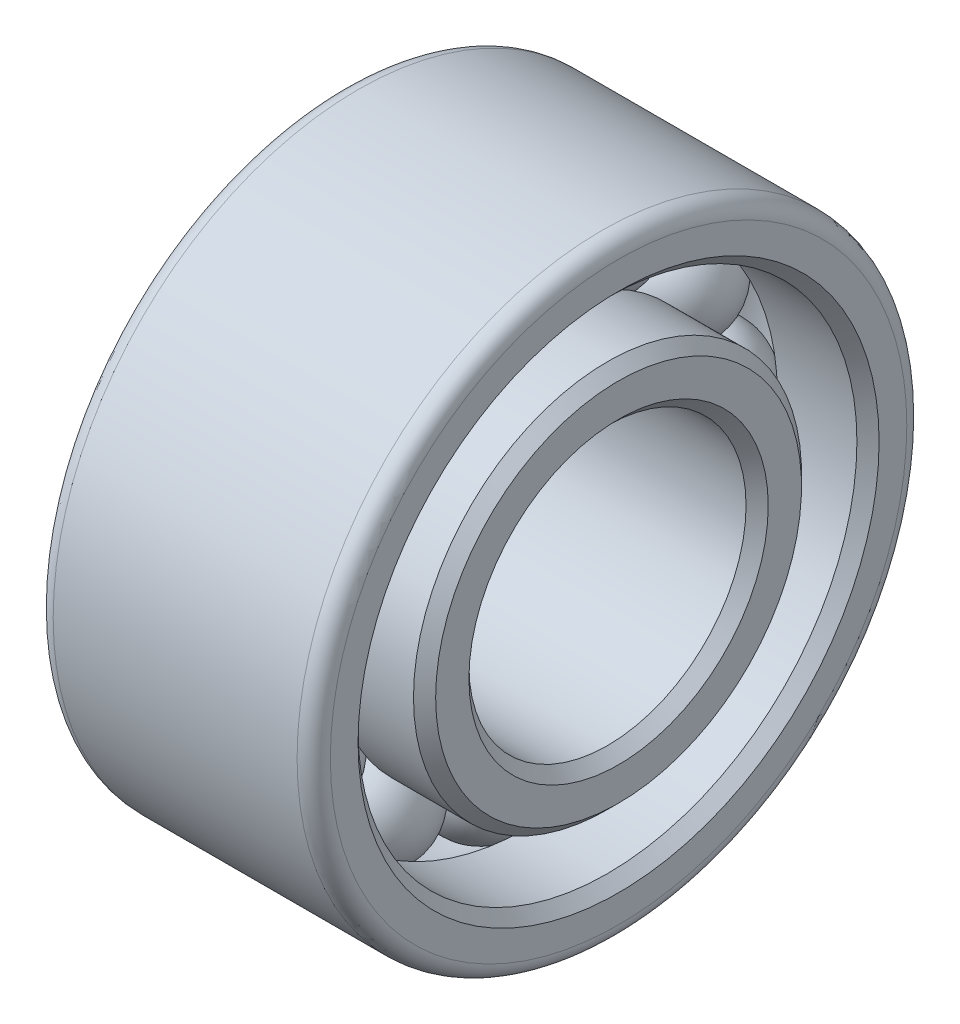
SolidWorks part; units mm, degrees
material "1023 Листовая углеродистая сталь (SS)"
ref_plane "Спереди" through (0, 0, 0) normal (0, 0, 1) x (1, 0, 0)
ref_plane "Сверху" through (0, 0, 0) normal (0, 1, 0) x (1, 0, 0)
ref_plane "Справа" through (0, 0, 0) normal (1, 0, 0) x (0, 0, -1)
sketch "Эскиз1" plane through (0, 0, 0) normal (0, 0, 1) x (1, 0, 0)
  line L0 (-1.0669, -2.5) -> (5.2077, -2.5) construction
  line L1 (0, 0) -> (5, 0)
  line L2 (0, 0) -> (0, 1)
  line L3 (0, 2) -> (1.634, 2)
  line L4 (5, 0) -> (5, 1)
  line L5 (5, 1) -> (3.366, 1)
  line L6 (0, 2) -> (0, 3)
  line L7 (0, 3) -> (5, 3)
  line L8 (5, 2) -> (5, 3)
  line L9 (3.366, 2) -> (5, 2)
  line L10 (1.634, 1) -> (0, 1)
  arc A0 (1.634, 1) -> (3.366, 1) centre (2.5, 1.5) ccw
  arc A1 (3.366, 2) -> (1.634, 2) centre (2.5, 1.5) ccw
  dimension "D7" = 5
  dimension "D2" = 2
  dimension "D8" = 0.5
  dimension "D1" = 2.5
  dimension "D3" = 1
  dimension "D4" = 5
  dimension "D5" = 1
  dimension "D6" = 5.5
revolve "Повернуть1" add sketch "Эскиз1" angle 360 about L0
sketch "Эскиз2" plane through (0, 0, 0) normal (0, 0, 1) x (1, 0, 0)
  line L0 (2.5, 2.5) -> (2.5, 0.5) construction
  line L1 (2.5, 2.5) -> (2.5, 0.5)
  line L2 (5, 3) -> (0, 3) construction
  line L3 (0, 3) -> (0, -8) construction
  arc A0 (2.5, 2.5) -> (2.5, 0.5) centre (2.5, 1.5) ccw
  dimension "D1" = 1
  dimension "D2" = 1.5
  dimension "D3" = 2.5
revolve "Повернуть2" add sketch "Эскиз2" angle 360 about L0
pattern_circular "Круговой массив5" count 12 over 360 about axis through (0, -2.5, 0) along (-1, 0, 0) of bodies 105
fillet "Скругление1" radius 0.3 2 edges at (5, -2.5, 5.5) (0, -2.5, 5.5)
chamfer "Фаска1" distance 0.2 angle 45 2 edges at (0, -2.5, 2.5) (5, -2.5, 2.5)
chamfer "Фаска2" distance 0.2 angle 45 2 edges at (5, -2.5, 3.5) (0, -2.5, 3.5)
chamfer "Фаска3" distance 0.2 angle 45 2 edges at (0, -2.5, 4.5) (5, -2.5, 4.5)
ref_plane "Plane1" through (2.5, 0, 0) normal (1, 0, 0) x (0, 0, -1)
sketch "Sketch1" plane through (2.5, 0, 0) normal (1, 0, 0) x (0, 0, -1)
  point P0 (0, -2.5)
